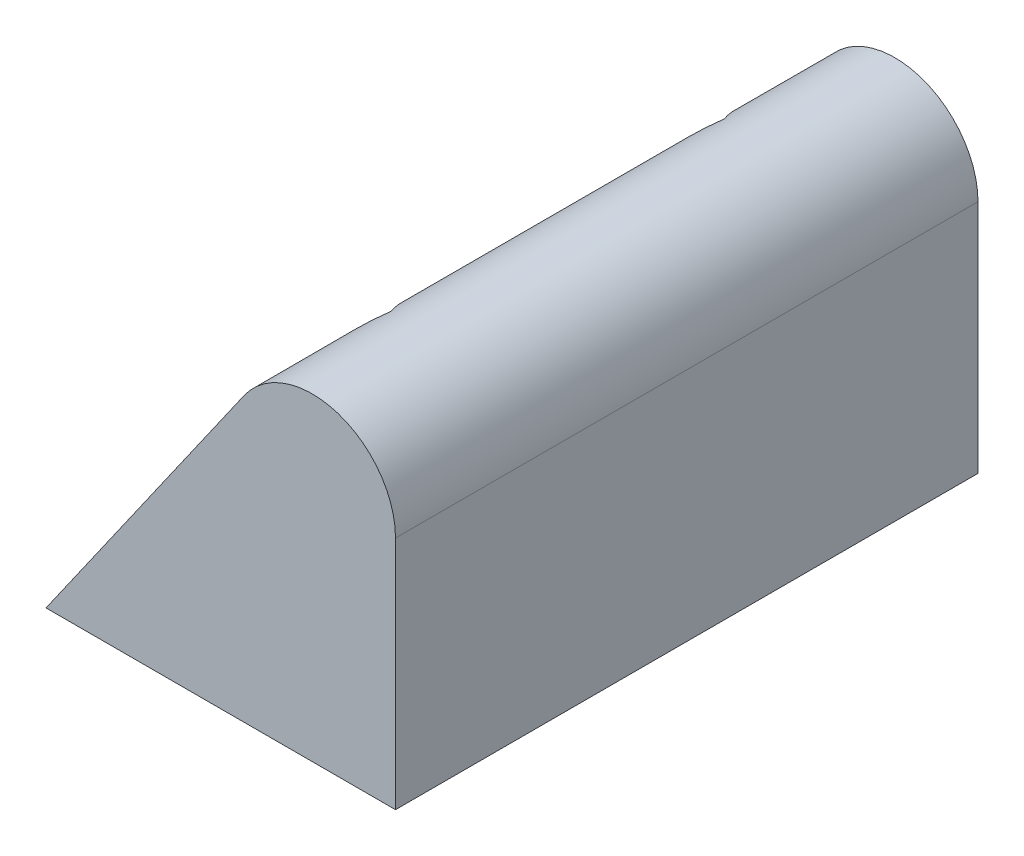
SolidWorks part; units mm, degrees
ref_plane "Front Plane" through (0, 0, 0) normal (0, 0, 1) x (1, 0, 0)
ref_plane "Top Plane" through (0, 0, 0) normal (0, 1, 0) x (1, 0, 0)
ref_plane "Right Plane" through (0, 0, 0) normal (1, 0, 0) x (0, 0, -1)
sketch "Sketch1" plane through (0, 0, 0) normal (0, 0, 1) x (1, 0, 0)
  line L0 (0, 0) -> (21, 30)
  line L1 (21, 30) -> (21, 0)
  line L2 (21, 0) -> (0, 0)
  dimension "D1" = 30
  dimension "D2" = 21
extrude "Boss-Extrude1" add sketch "Sketch1" along normal blind 35
sketch "Sketch2" plane through (0, 0, 0) normal (0, -1, 0) x (1, 0, 0)
  line L0 (21, 35) -> (21, 0) construction
  line L1 (0, 17.5) -> (21, 17.5) construction
  line L2 (0, 35) -> (0, 0) construction
  circle A0 centre (10, 27.5) radius 1.6
  circle A1 centre (10, 7.5) radius 1.6
  point P8 (22, 15)
  dimension "D1" = 3.2
  dimension "D2" = 20
  dimension "D3" = 11
extrude "Cut-Extrude1" cut sketch "Sketch2" against normal through all
sketch "Sketch3" plane through (0, 0, 0) normal (0, -1, 0) x (1, 0, 0)
  line L1 (13.2332, 27.5) -> (11.6166, 30.3)
  line L2 (11.6166, 30.3) -> (8.3834, 30.3)
  line L3 (8.3834, 30.3) -> (6.7668, 27.5)
  line L4 (6.7668, 27.5) -> (8.3834, 24.7)
  line L5 (8.3834, 24.7) -> (11.6166, 24.7)
  line L6 (11.6166, 24.7) -> (13.2332, 27.5)
  line L7 (13.2332, 7.5) -> (11.6166, 10.3)
  line L8 (11.6166, 10.3) -> (8.3834, 10.3)
  line L9 (8.3834, 10.3) -> (6.7668, 7.5)
  line L10 (6.7668, 7.5) -> (8.3834, 4.7)
  line L11 (8.3834, 4.7) -> (11.6166, 4.7)
  line L12 (11.6166, 4.7) -> (13.2332, 7.5)
  circle A0 centre (10, 27.5) radius 2.8 construction
  circle A1 centre (10, 7.5) radius 2.8 construction
  dimension "D1" = 5.6
extrude "Cut-Extrude2" cut sketch "Sketch3" against normal through all from offset 3 offset against normal yes
fillet "Fillet1" radius 5 1 edges at (21, 30, 17.5)
